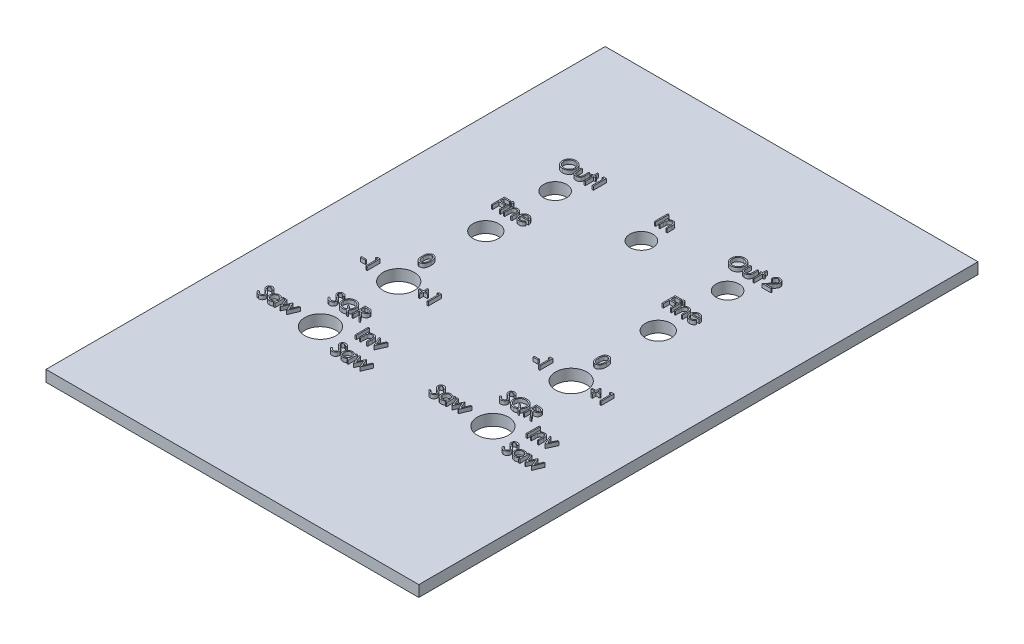
SolidWorks part; units mm, degrees
ref_plane "Front Plane" through (0, 0, 0) normal (0, 0, 1) x (1, 0, 0)
ref_plane "Top Plane" through (0, 0, 0) normal (0, 1, 0) x (1, 0, 0)
ref_plane "Right Plane" through (0, 0, 0) normal (1, 0, 0) x (0, 0, -1)
sketch "Sketch1" plane through (0, 0, 0) normal (0, 1, 0) x (1, 0, 0)
  line L0 (0, -1000) -> (0, 49000) construction
  line L1 (-50, -75) -> (50, -75)
  line L2 (-50, -75) -> (-50, 75)
  line L3 (-50, 75) -> (50, 75)
  line L4 (50, -75) -> (50, 75)
  line L5 (-50, -75) -> (50, 75) construction
  line L6 (-50, 75) -> (50, -75) construction
  circle A0 centre (-23.1316, 34.6975) radius 3.1
  circle A1 centre (0, 34.6975) radius 3.1
  circle A4 centre (23.1316, 34.6975) radius 3.1
  circle A5 centre (-23.1316, -28.2539) radius 4.2
  circle A7 centre (23.1316, -28.2539) radius 4.2
  circle A8 centre (-23.1316, -7.2599) radius 4.2
  circle A9 centre (23.1316, -7.2599) radius 4.2
  circle A10 centre (-23.1316, 16.1025) radius 3.45
  circle A11 centre (23.1316, 16.1025) radius 3.45
  point P0 (0, 0)
  dimension "D3" = 6.2
  dimension "D4" = 6.2
  dimension "D5" = 8.4
  dimension "D6" = 8.4
  dimension "D7" = 6.9
  dimension "D9" = 26.8684
  dimension "D12" = 46.7461
  dimension "D13" = 20.9941
  dimension "D14" = 23.3623
  dimension "D15" = 40.3025
  dimension "D1" = 100
  dimension "D2" = 150
  dimension "D8" = 26.8684
  dimension "D10" = 26.8684
  dimension "D11" = 26.8684
extrude "Boss-Extrude2" add sketch "Sketch1" along normal blind 3
sketch "Sketch2" plane through (0, 3, 0) normal (0, 1, 0) x (1, 0, 0)
  line L0 (-50, 75) -> (-50, -75) construction
  line L1 (50, 75) -> (-50, 75) construction
  line L3 (-50, -75) -> (50, -75) construction
  text T0 "Out1           In           Out 2"
  text T1 "Fine                           Fine  "
  text T2 "0                                 0 "
  text T3 "-1        +1                   -1        +1"
  text T4 "SQR                           SQR"
  text T5 "Saw                           Saw"
  text T6 "Inv                             Inv\r\nSaw                           Saw"
  point P1 (-25.4598, 40.7163)
  dimension "D1" = 21.5
  dimension "D2" = 35
  dimension "D3" = 22
  dimension "D4" = 53
  dimension "D5" = 25
  dimension "D6" = 76
  dimension "D7" = 17
  dimension "D8" = 53
  dimension "54" = 66
  dimension "D9" = 22
  dimension "D10" = 45
  dimension "D11" = 11
  dimension "D12" = 48.5
  dimension "D13" = 34
extrude "Boss-Extrude3" add sketch "Sketch2" along normal blind 1
